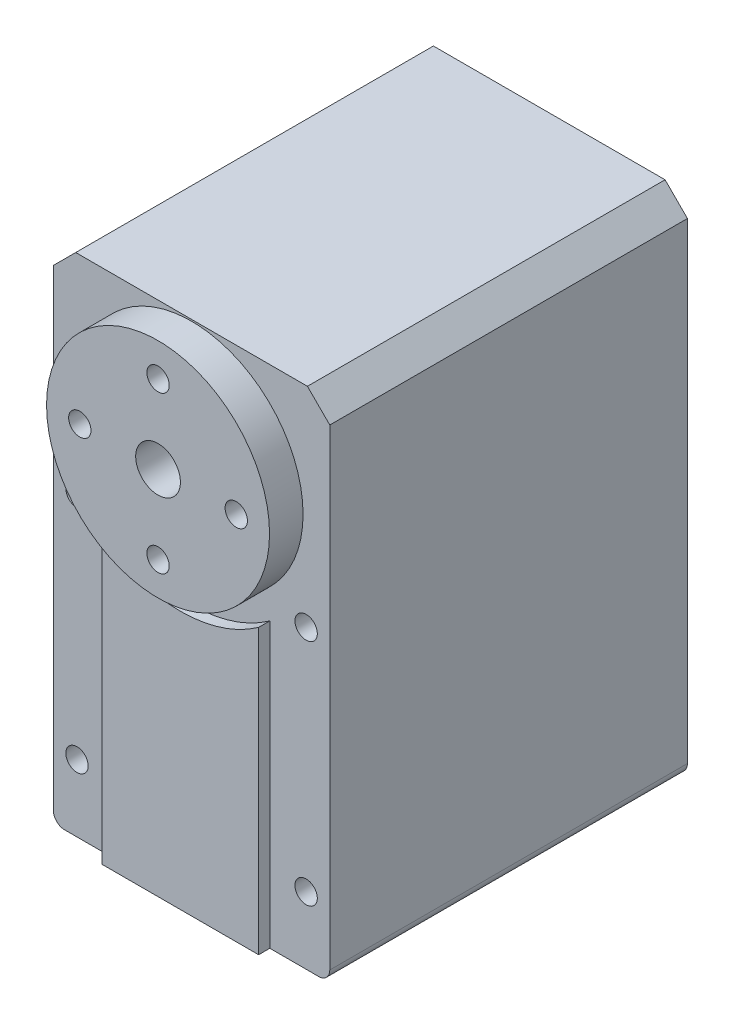
SolidWorks part; units mm, degrees
ref_plane "정면" through (0, 0, 0) normal (0, 0, 1) x (1, 0, 0)
ref_plane "윗면" through (0, 0, 0) normal (0, 1, 0) x (1, 0, 0)
ref_plane "우측면" through (0, 0, 0) normal (1, 0, 0) x (0, 0, -1)
sketch "스케치1" plane through (0, 0, 0) normal (0, 0, 1) x (1, 0, 0)
  line L1 (-12.365, 22.615) -> (12.365, 22.615)
  line L2 (-12.365, 22.615) -> (-12.365, -22.615)
  line L3 (-12.365, -22.615) -> (12.365, -22.615)
  line L4 (12.365, 22.615) -> (12.365, -22.615)
  line L5 (-12.365, 22.615) -> (12.365, -22.615) construction
  line L6 (-12.365, -22.615) -> (12.365, 22.615) construction
  point P0 (0, 0)
  dimension "D1" = 24.73
  dimension "D2" = 45.23
extrude "보스-돌출1" add sketch "스케치1" along normal blind 32
chamfer "모따기1" distance 2 angle 45 2 edges at (-12.365, 22.615, 16) (12.365, 22.615, 16)
sketch "스케치2" plane through (0, 0, 32) normal (0, 0, 1) x (1, 0, 0)
  line L0 (-12.365, -22.615) -> (12.365, -22.615) construction
  line L1 (-7, -22.615) -> (7, -22.615)
  line L2 (-7, -22.615) -> (-7, 2.7532)
  line L4 (7, -22.615) -> (7, 2.7532)
  arc A0 (-7, 2.7532) -> (7, 2.7532) centre (0, 12.5) ccw
  dimension "D4" = 24
  dimension "D1" = 14
  dimension "D2" = 7
  dimension "D3" = 12.5
extrude "보스-돌출2" add sketch "스케치2" along normal blind 1
sketch "스케치3" plane through (0, 0, 32) normal (0, 0, 1) x (1, 0, 0)
  line L0 (7, -22.615) -> (12.365, -22.615) construction
  line L1 (-10.25, -16.615) -> (10.25, -16.615) construction
  line L2 (-10.25, -16.615) -> (-10.25, 3.885) construction
  line L3 (-10.25, 3.885) -> (10.25, 3.885) construction
  line L4 (10.25, -16.615) -> (10.25, 3.885) construction
  circle A0 centre (-10.25, 3.885) radius 1
  circle A1 centre (-10.25, -16.615) radius 1
  circle A2 centre (10.25, -16.615) radius 1
  circle A3 centre (10.25, 3.885) radius 1
  dimension "D5" = 2
  dimension "D1" = 20.5
  dimension "D2" = 20.5
  dimension "D3" = 6
  dimension "D4" = 10.25
extrude "컷-돌출1" cut sketch "스케치3" against normal blind 4
sketch "스케치4" plane through (0, 0, 32) normal (0, 0, 1) x (1, 0, 0)
  circle A0 centre (0, 12.5) radius 9.975
  dimension "D1" = 12.5
  dimension "D2" = 19.95
extrude "보스-돌출3" add sketch "스케치4" along normal blind 3
sketch "스케치5" plane through (0, 0, 35) normal (0, 0, 1) x (1, 0, 0)
  circle A0 centre (0, 12.5) radius 7 construction
  circle A5 centre (0, 12.5) radius 2
  circle A6 centre (0, 19.5) radius 1
  circle A7 centre (7, 12.5) radius 1
  circle A8 centre (0, 12.5) radius 7 construction
  circle A9 centre (0, 5.5) radius 1
  circle A10 centre (0, 12.5) radius 7 construction
  circle A11 centre (-7, 12.5) radius 1
  circle A12 centre (0, 12.5) radius 7 construction
  point P18 (0, 12.5)
  dimension "D1" = 14
  dimension "D2" = 2
  dimension "D3" = 4
  dimension "D4" = 4
extrude "컷-돌출2" cut sketch "스케치5" against normal blind 3
sketch "스케치6" plane through (0, 0, 0) normal (0, 0, -1) x (-1, 0, 0)
  line L0 (-12.365, -22.615) -> (-12.365, 20.615) construction
  line L1 (-10.165, -18.115) -> (10.165, -18.115)
  line L2 (-10.165, -18.115) -> (-10.165, -6.115)
  line L3 (-10.165, -6.115) -> (10.165, -6.115)
  line L4 (10.165, -18.115) -> (10.165, -6.115)
  line L5 (12.365, 20.615) -> (12.365, -22.615) construction
  line L6 (12.365, -22.615) -> (-12.365, -22.615) construction
  dimension "D1" = 2.2
  dimension "D2" = 2.2
  dimension "D3" = 4.5
  dimension "D4" = 12
extrude "보스-돌출4" add sketch "스케치6" along normal blind 2
chamfer "모따기2" distance 2 angle 45 1 edges at (0, -6.115, -2)
sketch "스케치7" plane through (0, 0, 0) normal (0, 0, -1) x (-1, 0, 0)
  line L0 (12.365, 20.615) -> (12.365, -22.615) construction
  line L1 (11.165, -6.115) -> (-11.165, -6.115)
  line L2 (11.165, -6.115) -> (11.165, -1.115)
  line L3 (11.165, -1.115) -> (-11.165, -1.115)
  line L4 (-11.165, -6.115) -> (-11.165, -1.115)
  line L5 (-12.365, -22.615) -> (-12.365, 20.615) construction
  line L6 (10.165, -6.115) -> (-10.165, -6.115) construction
  dimension "D1" = 1.2
  dimension "D2" = 1.2
  dimension "D3" = 5
extrude "컷-돌출3" cut sketch "스케치7" against normal blind 2
sketch "스케치8" plane through (0, 0, 0) normal (0, 0, -1) x (-1, 0, 0)
  circle A0 centre (0, 12.5) radius 3
  dimension "D1" = 12.5
  dimension "D2" = 6
extrude "보스-돌출5" add sketch "스케치8" along normal blind 4.1
sketch "스케치9" plane through (0, 0, 0) normal (0, 0, -1) x (-1, 0, 0)
  line L0 (12.365, -22.615) -> (-12.365, -22.615) construction
  line L1 (-10.25, -20.615) -> (10.25, -20.615) construction
  line L2 (-10.25, -20.615) -> (-10.25, 3.885) construction
  line L3 (-10.25, 3.885) -> (10.25, 3.885) construction
  line L4 (10.25, -20.615) -> (10.25, 3.885) construction
  circle A0 centre (-10.25, 3.885) radius 1
  circle A1 centre (10.25, 3.885) radius 1
  circle A2 centre (-10.25, -20.615) radius 1
  circle A3 centre (10.25, -20.615) radius 1
  dimension "D5" = 2
  dimension "D1" = 20.5
  dimension "D2" = 24.5
  dimension "D3" = 10.25
  dimension "D4" = 2
extrude "컷-돌출4" cut sketch "스케치9" against normal blind 4
fillet "필렛1" radius 1 2 edges at (-12.365, -22.615, 16) (12.365, -22.615, 16)
